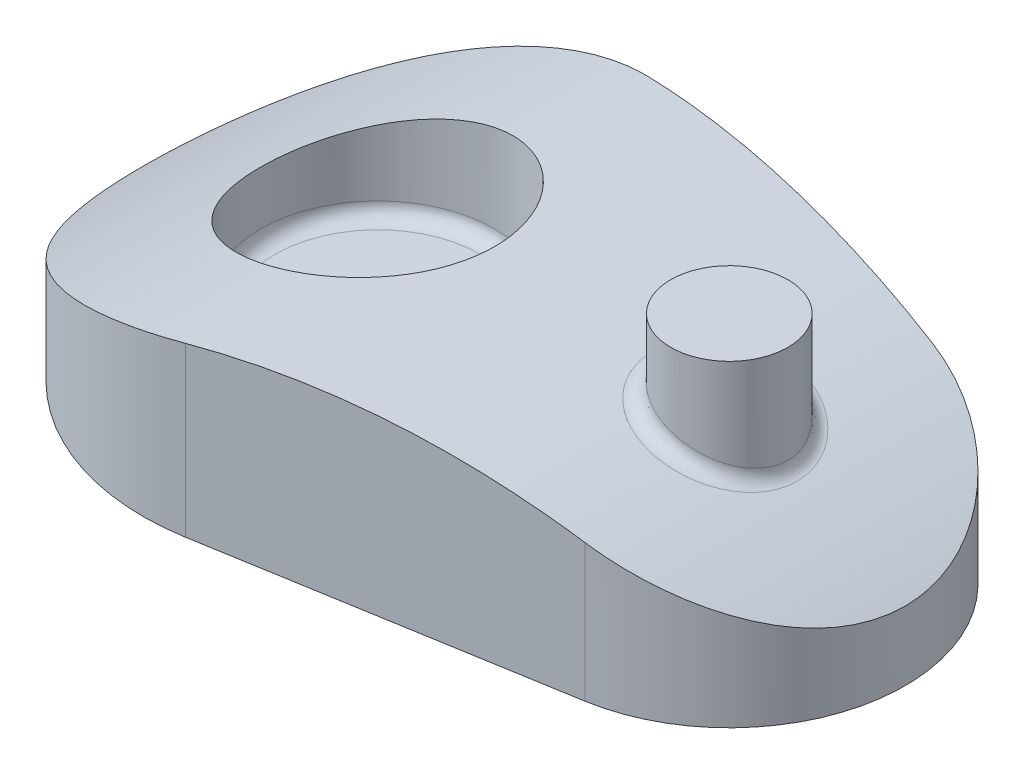
SolidWorks part; units mm, degrees
ref_plane "정면" through (0, 0, 0) normal (0, 0, 1) x (1, 0, 0)
ref_plane "윗면" through (0, 0, 0) normal (0, 1, 0) x (1, 0, 0)
ref_plane "우측면" through (0, 0, 0) normal (1, 0, 0) x (0, 0, -1)
sketch "스케치3" plane through (0, 0, 0) normal (0, 1, 0) x (1, 0, 0)
  line L0 (0, 0) -> (-179.432, 0) construction
  line L1 (-53.3333, 39.4405) -> (5, 29.5804)
  line L2 (-53.3333, -39.4405) -> (5, -29.5804)
  arc A0 (5, -29.5804) -> (5, 29.5804) centre (0, 0) ccw
  arc A1 (-53.3333, 39.4405) -> (-53.3333, -39.4405) centre (-60, 0) ccw
  dimension "D1" = 60
  dimension "D2" = 80
  dimension "D3" = 60
extrude "보스-돌출1" add sketch "스케치3" along normal blind 100
sketch "스케치5" plane through (0, 0, 0) normal (0, 0, 1) x (1, 0, 0)
  line L0 (-100, 100) -> (-100, 0) construction
  line L1 (30, 0) -> (30, 100) construction
  line L2 (-292.9483, 30) -> (249.6398, 30) construction
  line L3 (-100, 11.7708) -> (-182.7476, 155.0939)
  line L4 (-182.7476, 155.0939) -> (117.2524, 155.0939)
  line L5 (117.2524, 155.0939) -> (30, 11.7708)
  arc A0 (30, 11.7708) -> (-100, 11.7708) centre (-35, -95) ccw
  point P10 (-100, 11.6782)
  point P12 (39.63, 5.2764)
  dimension "D2" = 30
  dimension "D3" = 250
  dimension "D4" = 0
  dimension "D1" = 65
  dimension "D5" = 60
  dimension "D6" = 0
  dimension "D7" = 300
extrude "컷-돌출1" cut sketch "스케치5" against normal mid plane 100
ref_plane "평면1" through (0, 10, 0) normal (0, -1, 0) x (-1, 0, 0)
sketch "스케치7" plane through (0, 10, 0) normal (0, -1, 0) x (-1, 0, 0)
  circle A0 centre (0, 0) radius 10
  arc A1 (-5, 29.5804) -> (-5, -29.5804) centre (0, 0) ccw construction
  dimension "D1" = 20
extrude "보스-돌출2" add sketch "스케치7" against normal blind 30
fillet "필렛1" radius 2.5 1 edges at (-2.4007, 25.6743, 9.7075)
sketch "스케치8" plane through (0, 10, 0) normal (0, -1, 0) x (-1, 0, 0)
  circle A0 centre (60, 0) radius 20
  arc A1 (53.3333, -39.4405) -> (53.3333, 39.4405) centre (60, 0) ccw construction
  dimension "D1" = 40
extrude "컷-돌출2" cut sketch "스케치8" against normal blind 30
fillet "필렛2" radius 2.5 1 edges at (-60, 10, -20)
